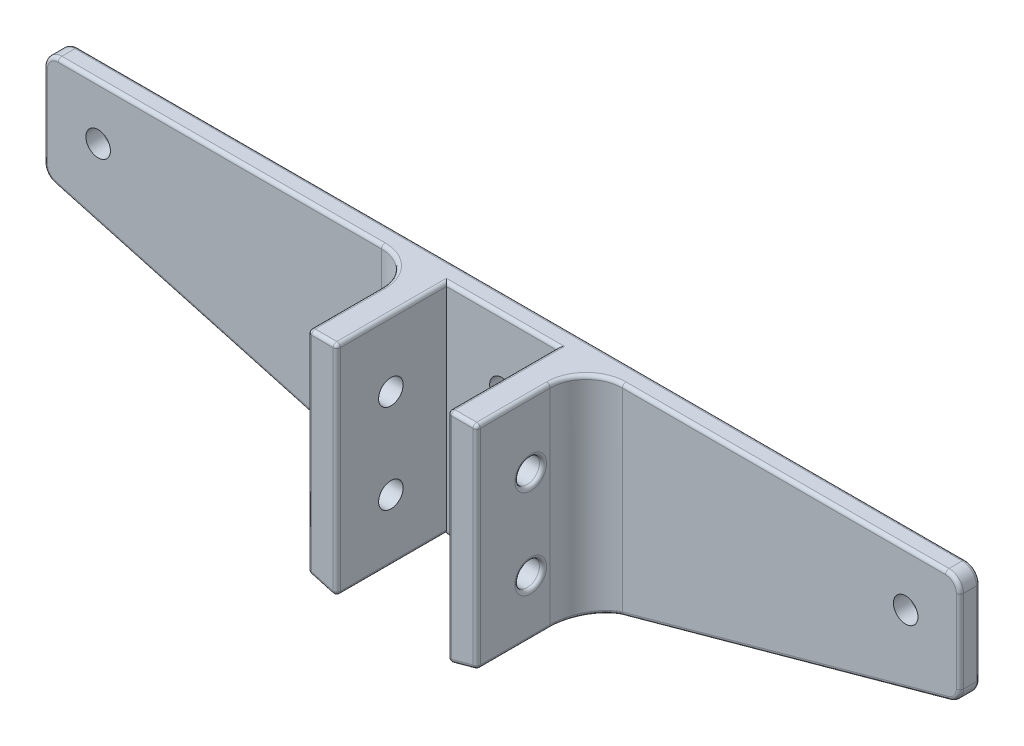
SolidWorks part; units mm, degrees
ref_plane "Front Plane" through (0, 0, 0) normal (0, 0, 1) x (1, 0, 0)
ref_plane "Top Plane" through (0, 0, 0) normal (0, 1, 0) x (1, 0, 0)
ref_plane "Right Plane" through (0, 0, 0) normal (1, 0, 0) x (0, 0, -1)
sketch "Sketch1" plane through (0, 0, 0) normal (0, 0, 1) x (1, 0, 0)
  line L0 (0, 0) -> (0, -127.5265) construction
  line L1 (63.5265, -127.5265) -> (-63.5265, -127.5265) construction
  line L2 (63.5265, -112.5265) -> (-63.5265, -112.5265)
  line L3 (-63.5265, -127.5265) -> (-63.5265, 127.5265) construction
  line L4 (-63.5265, -112.5265) -> (-63.5265, -127.5265)
  line L5 (-63.5265, -127.5265) -> (-7.4, -143)
  line L6 (-7.4, -143) -> (7.4, -143)
  line L7 (-7.4, -128) -> (-7.4, -428) construction
  line L8 (7.4, -128) -> (1.8, -128) construction
  line L9 (63.5265, -127.5265) -> (7.4, -143)
  line L10 (63.5265, -112.5265) -> (63.5265, -127.5265)
  circle A0 centre (-56, -120.0265) radius 1.32 construction
  circle A1 centre (56, -120.0265) radius 1.32 construction
  circle A2 centre (-56, -120.0265) radius 1.32 construction
  circle A3 centre (56, -120.0265) radius 1.32 construction
  circle A4 centre (-56, -120.0265) radius 1.7
  circle A5 centre (56, -120.0265) radius 1.7
  point P31 (0, -143)
  point P33 (0, -112.5265)
  dimension "D1" = 3.4
  dimension "D2" = 7.5
  dimension "D3" = 15
  dimension "D4" = 7.5
extrude "Boss-Extrude1" add sketch "Sketch1" along normal offset from surface (2.8 mm away) 0.2
sketch "Sketch3" plane through (0, -112.5265, 0) normal (0, 1, 0) x (1, 0, 0)
  line L0 (-7.5, -8.7) -> (-7.5, -3.1) construction
  line L1 (-7.7, -18) -> (-7.7, -2.8)
  line L2 (-63.5265, -2.8) -> (63.5265, -2.8) construction
  line L3 (-7.7, -2.8) -> (-11.7, -2.8)
  line L4 (-11.7, -2.8) -> (-11.7, -18)
  line L5 (-11.7, -18) -> (-7.7, -18)
  line L6 (0, 0) -> (0, -28.7121) construction
  line L8 (-1.8, -18) -> (-7.4, -18) construction
  dimension "D1" = 4
  dimension "D2" = 0.2
extrude "Boss-Extrude2" add sketch "Sketch3" against normal up to surface (30.4735 mm away) up to face at (0, -143, 1.4)
fillet "Fillet1" radius 5 1 edges at (-11.7, -127.1705, 2.8)
mirror "Mirror1" about plane through (0, 0, 0) normal (1, 0, 0) of "Boss-Extrude2", "Fillet1"
sketch "Sketch4" plane through (0, 0, 0) normal (0, 0, -1) x (-1, 0, 0)
  line L0 (-7.4, -143) -> (-63.5265, -127.5265) construction
  line L1 (7.4, -143) -> (-7.4, -143) construction
  line L2 (63.5265, -127.5265) -> (7.4, -143) construction
  line L3 (-7.4, -143) -> (-63.5265, -127.5265)
  line L4 (7.4, -143) -> (-7.4, -143)
  line L5 (63.5265, -127.5265) -> (7.4, -143)
  line L6 (-63.5265, -127.5265) -> (-63.5265, -166.5065)
  line L7 (-63.5265, -166.5065) -> (63.5265, -166.5065)
  line L8 (63.5265, -166.5065) -> (63.5265, -127.5265)
extrude "Cut-Extrude1" cut sketch "Sketch4" against normal through all both and the other way through all
sketch "Sketch5" plane through (0, 0, 0) normal (1, 0, 0) x (0, 0, -1)
  line L0 (-18, -428) -> (-18, -128) construction
  line L1 (-3, -128) -> (-3, -428) construction
  line L2 (-18, -428) -> (-18, -128) construction
  line L3 (-3, -128) -> (-3, -428) construction
  line L4 (-18, -128) -> (-3, -128) construction
  line L5 (-10.5, -112.5265) -> (-10.5, -141.8145) construction
  line L6 (-7.8, -112.5265) -> (-18, -112.5265) construction
  line L7 (-18, -141.8145) -> (-7.8, -141.8145) construction
  circle A0 centre (-10.5, -134.1894) radius 1.7
  circle A1 centre (-10.5, -121.8106) radius 1.7
  point P15 (-10.5, -128)
  dimension "D1" = 3.4
  dimension "D2" = 15.4735
  dimension "D3" = 6.1894
extrude "Cut-Extrude2" cut sketch "Sketch5" against normal through all both and the other way through all
ref_plane "Plane4" through (0, 0, 10.5) normal (0, 0, 1) x (1, 0, 0)
ref_axis "Axis1" through (0, -111.0028, 10.5) along (0, -1, 0)
pattern_circular "CirPattern1" count 2 every 90 about axis through (0, -111.0028, 10.5) along (0, -1, 0) of "Cut-Extrude2"
fillet "Fillet2" radius 2 6 edges at (7.4, -143, 1.4) (-7.4, -143, 1.4) (-63.5265, -127.5265, 1.4) (-63.5265, -112.5265, 1.4) (63.5265, -127.5265, 1.4) (63.5265, -112.5265, 1.4)
fillet "Fillet3" radius 0.5 56 edges at (-7.3976, -142.9819, 2.8) (0, -143, 2.8) (7.3976, -142.9819, 2.8) (63.1176, -127.215, 2.8) (63.5265, -120.2649, 2.8) (62.9407, -113.1123, 2.8) (-63.1176, -127.215, 2.8) (-63.5265, -120.2649, 2.8) (-62.9407, -113.1123, 2.8) (-11.7, -123.5106, 10.5) (-11.7, -135.8894, 10.5) (11.7, -123.5106, 10.5) (11.7, -135.8894, 10.5) (54.3, -120.0265, 0) (-54.3, -120.0265, 0) (63.1176, -127.215, 0) (63.5265, -120.2649, 0) (62.9407, -113.1123, 0) (-62.9407, -113.1123, 0) (-63.5265, -120.2649, 0) (-63.1176, -127.215, 0) (-7.3976, -142.9819, 0) (0, -143, 0) (7.3976, -142.9819, 0) (-1.7, -121.8106, 0) (1.7, -134.1894, 0) (11.7, -127.1705, 18) (7.7, -127.7219, 18) (-11.7, -127.1705, 18) (-7.7, -127.7219, 18) (-39.379, -134.1837, 2.8) (-13.1645, -141.4108, 4.2645) (-11.7, -141.8145, 12.9) (-9.7, -142.3659, 18) (-7.7, -142.9173, 10.4) (-7.6805, -142.9227, 2.8) (-34.8595, -135.4297, 0) (7.7, -142.9173, 10.4) (9.7, -142.3659, 18) (11.7, -141.8145, 12.9) (13.1645, -141.4108, 4.2645) (39.379, -134.1837, 2.8) (34.8595, -135.4297, 0) (7.6805, -142.9227, 2.8) (39.1132, -112.5265, 2.8) (13.1645, -112.5265, 4.2645) (11.7, -112.5265, 12.9) (9.7, -112.5265, 18) (7.7, -112.5265, 10.4) (0, -112.5265, 2.8) (-7.7, -112.5265, 10.4) (-9.7, -112.5265, 18) (-11.7, -112.5265, 12.9) (-13.1645, -112.5265, 4.2645) (-39.1132, -112.5265, 2.8) (0, -112.5265, 0)
ref_plane "Plane5" through (0, 0, 10.5) normal (0, 0, 1) x (1, 0, 0)
equation "\"D1@Sketch1\"=3mm + .4mm"
equation "\"D4@Sketch1\"=\"D2@Sketch1\""
equation "\"beam interface clearance\"= .2mm"
equation "\"D1@Boss-Extrude1\"=\"beam interface clearance\""
equation "\"D2@Sketch3\"=\"beam interface clearance\""
equation "\"screw clearance\"= .4"
equation "\"D1@Sketch5\"=\"screw clearance\"+3"
equation "\"D3@Sketch5\"=\"D2@Sketch5\"*2/5"
